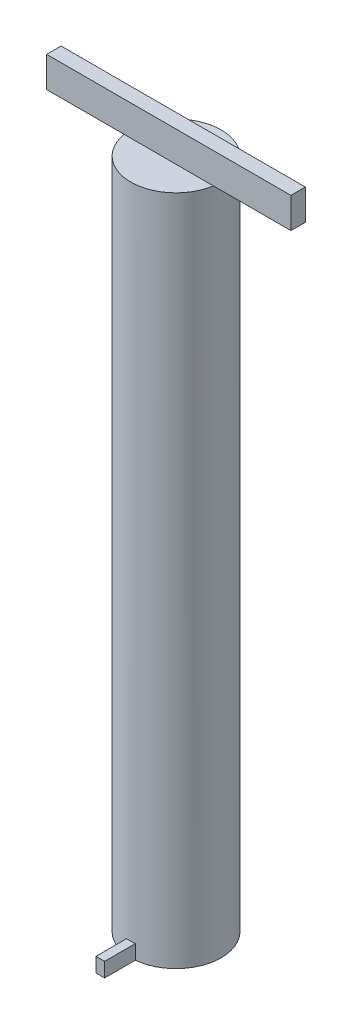
SolidWorks part; units mm, degrees
ref_plane "Front Plane" through (0, 0, 0) normal (0, 0, 1) x (1, 0, 0)
ref_plane "Top Plane" through (0, 0, 0) normal (0, 1, 0) x (1, 0, 0)
ref_plane "Right Plane" through (0, 0, 0) normal (1, 0, 0) x (0, 0, -1)
sketch "Sketch1" plane through (0, 0, 0) normal (0, 1, 0) x (1, 0, 0)
  circle A0 centre (0, 0) radius 9.398
  dimension "D1" = 18.796
extrude "Boss-Extrude1" add sketch "Sketch1" along normal blind 139.7
sketch "Sketch3" plane through (0, 0, 0) normal (0, -1, 0) x (1, 0, 0)
  line L1 (-0.9, 15.75) -> (0.9, 15.75)
  line L2 (-0.9, 15.75) -> (-0.9, 9.3548)
  line L4 (0.9, 15.75) -> (0.9, 9.3548)
  arc A0 (0.9, 9.3548) -> (-0.9, 9.3548) centre (0, 0) ccw
  dimension "D1" = 0.9
  dimension "D3" = 15.75
extrude "Boss-Extrude2" add sketch "Sketch3" against normal blind 3
sketch "Sketch4" plane through (0, 139.7, 0) normal (0, 1, 0) x (1, 0, 0)
  line L1 (-25.4, 1.5) -> (25.4, 1.5)
  line L2 (-25.4, 1.5) -> (-25.4, -1.5)
  line L3 (-25.4, -1.5) -> (25.4, -1.5)
  line L4 (25.4, 1.5) -> (25.4, -1.5)
  point P4 (-25.4, 0)
  point P5 (0, 1.5)
  dimension "D1" = 50.8
  dimension "D2" = 3
extrude "Boss-Extrude3" add sketch "Sketch4" along normal blind 6.35
sketch "Sketch5" plane through (0, 0, 0) normal (0, -1, 0) x (1, 0, 0)
  circle A0 centre (0, 0) radius 2.5
  dimension "D1" = 5
extrude "Cut-Extrude1" cut sketch "Sketch5" against normal blind 2.54
